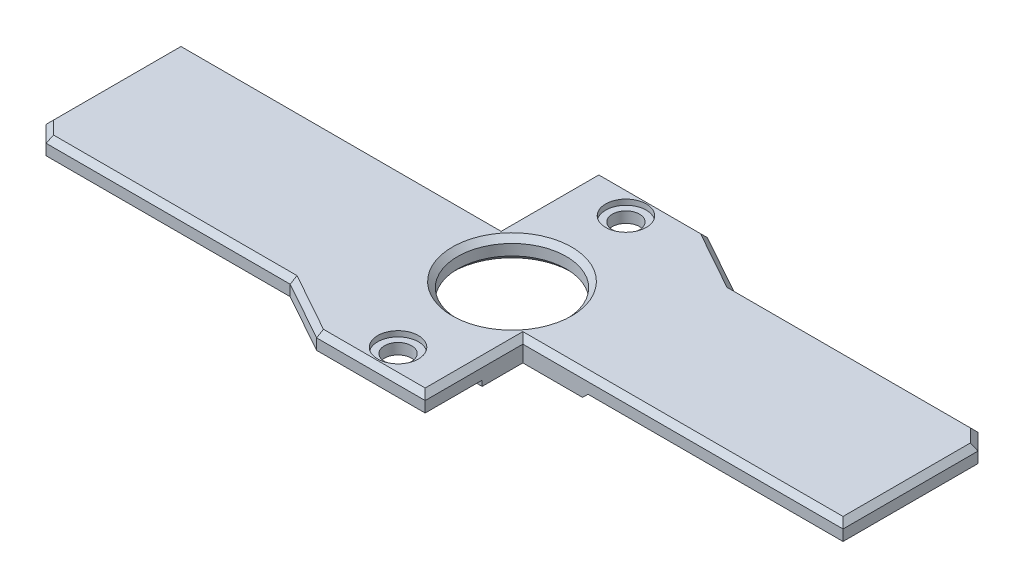
SolidWorks part; units mm, degrees
ref_plane "Front Plane" through (0, 0, 0) normal (0, 0, 1) x (1, 0, 0)
ref_plane "Top Plane" through (0, 0, 0) normal (0, 1, 0) x (1, 0, 0)
ref_plane "Right Plane" through (0, 0, 0) normal (1, 0, 0) x (0, 0, -1)
sketch "Sketch1" plane through (0, 0, 0) normal (0, 1, 0) x (1, 0, 0)
  line L1 (-21, -21) -> (21, -21)
  line L2 (-21, -21) -> (-21, 21)
  line L3 (-21, 21) -> (21, 21)
  line L4 (21, -21) -> (21, 21)
  line L5 (-21, -21) -> (21, 21) construction
  line L6 (-21, 21) -> (21, -21) construction
  point P0 (0, 0)
  dimension "D1" = 42
  dimension "D2" = 42
extrude "Boss-Extrude1" add sketch "Sketch1" along normal blind 2
sketch "Sketch2" plane through (0, 2, 0) normal (0, 1, 0) x (1, 0, 0)
  line L0 (0, 21) -> (0, -21) construction
  line L1 (21, 21) -> (-21, 21) construction
  line L2 (-21, -21) -> (21, -21) construction
  line L3 (-1.1, 0) -> (1.1, 0) construction
  line L4 (-10, -26) -> (10, -26)
  line L5 (-10, -26) -> (-10, -16)
  line L6 (-10, -16) -> (10, -16)
  line L7 (10, -26) -> (10, -16)
  line L8 (-10, -26) -> (10, -16) construction
  line L9 (-10, -16) -> (10, -26) construction
  line L14 (-10, 16) -> (10, 16)
  line L15 (10, 26) -> (10, 16)
  line L16 (-10, 26) -> (10, 26)
  line L17 (-10, 26) -> (-10, 16)
  dimension "D1" = 10
  dimension "D2" = 20
extrude "Boss-Extrude2" add sketch "Sketch2" against normal up to surface (2 mm away) up to face at (0, 0, 0)
sketch "Sketch3" plane through (0, 2, 0) normal (0, 1, 0) x (1, 0, 0)
  circle A0 centre (0, 0) radius 10
  dimension "D1" = 20
extrude "Cut-Extrude1" cut sketch "Sketch3" against normal blind 10
sketch "Sketch4" plane through (0, 2, 0) normal (0, 1, 0) x (1, 0, 0)
  line L0 (-21, 21) -> (-21, -21) construction
  line L1 (21, -21) -> (21, 21) construction
  line L2 (21, -8) -> (-10, -8) construction
  line L5 (0, -1.1) -> (0, 1.1) construction
  line L6 (10, -21) -> (21, -21) construction
  line L7 (21, -21) -> (10, -21)
  line L8 (21, -21) -> (21, -8)
  line L9 (21, -8) -> (10, -8)
  line L10 (10, -21) -> (10, -8)
  line L15 (-1.1, 0) -> (1.1, 0) construction
  line L16 (-21, 21) -> (-21, 8)
  line L17 (-21, 21) -> (-10, 21)
  line L18 (-10, 21) -> (-10, 8)
  line L19 (-21, 8) -> (-10, 8)
  dimension "D1" = 13
  dimension "D2" = 11
extrude "Cut-Extrude2" cut sketch "Sketch4" against normal blind 10
sketch "Sketch5" plane through (0, 2, 0) normal (0, 1, 0) x (1, 0, 0)
  line L0 (-1.1, 0) -> (1.1, 0) construction
  circle A0 centre (0, 21) radius 2.5
  circle A1 centre (0, -21) radius 2.5
  dimension "D1" = 5
extrude "Cut-Extrude3" cut sketch "Sketch5" against normal blind 10
chamfer "Chamfer1" distance 10 angle 45 2 edges at (21, 1, -21) (-21, 1, 21)
sketch "Sketch6" plane through (0, 2, 0) normal (0, 1, 0) x (1, 0, 0)
  line L18 (21, -8) -> (21, 11)
  line L19 (21, 11) -> (11, 21)
  line L20 (11, 21) -> (10, 21)
  line L21 (10, 21) -> (10, 26)
  line L22 (10, 26) -> (-10, 26)
  line L23 (-10, 26) -> (-10, 8)
  line L26 (-10, 8) -> (-21, 8)
  line L27 (-21, 8) -> (-21, -11)
  line L28 (-21, -11) -> (-11, -21)
  line L29 (-11, -21) -> (-10, -21)
  line L30 (-10, -21) -> (-10, -26)
  line L31 (-10, -26) -> (10, -26)
  line L32 (10, -26) -> (10, -8)
  line L35 (10, -8) -> (21, -8)
  line L36 (21, -8) -> (21, 11)
  line L37 (21, 11) -> (11, 21)
  line L38 (11, 21) -> (10, 21)
  line L39 (10, 21) -> (10, 26)
  line L40 (10, 26) -> (-10, 26)
  line L41 (-10, 26) -> (-10, 8)
  line L44 (-10, 8) -> (-21, 8)
  line L45 (-21, 8) -> (-21, -11)
  line L46 (-21, -11) -> (-11, -21)
  line L47 (-11, -21) -> (-10, -21)
  line L48 (-10, -21) -> (-10, -26)
  line L49 (-10, -26) -> (10, -26)
  line L50 (10, -26) -> (10, -8)
  line L53 (10, -8) -> (21, -8)
  circle A0 centre (0, 21) radius 3.75
  circle A1 centre (0, -21) radius 3.75
  circle A2 centre (0, 0) radius 10
  dimension "D2" = 7.5
  dimension "D1" = 0
extrude "Boss-Extrude3" add sketch "Sketch6" along normal blind 1
sketch "Sketch8" plane through (0, 0, 0) normal (0, -1, 0) x (1, 0, 0)
  line L1 (10, -15.5) -> (-10, -15.5)
  line L3 (-10, 15.5) -> (10, 15.5)
  line L4 (10, -26) -> (-10, -26) construction
  line L5 (-10, 26) -> (10, 26) construction
  line L6 (10, -15.5) -> (16.5, -15.5)
  line L7 (-10, 15.5) -> (-16.5, 15.5)
  line L14 (10, -21) -> (11, -21)
  line L15 (11, -21) -> (21, -11)
  line L16 (21, -11) -> (21, 8)
  line L17 (21, 8) -> (10, 8)
  line L18 (10, 8) -> (10, 26)
  line L19 (10, 26) -> (-10, 26)
  line L20 (-10, 26) -> (-10, 21)
  line L21 (-10, 21) -> (-11, 21)
  line L22 (-11, 21) -> (-21, 11)
  line L23 (-21, 11) -> (-21, -8)
  line L24 (-21, -8) -> (-10, -8)
  line L25 (-10, -8) -> (-10, -26)
  line L26 (-10, -26) -> (10, -26)
  line L27 (10, -26) -> (10, -21)
  line L29 (16.5, -15.5) -> (21, -11)
  line L30 (21, -11) -> (21, 8)
  line L31 (21, 8) -> (10, 8)
  line L32 (10, 8) -> (10, 15.5)
  line L36 (-16.5, 15.5) -> (-21, 11)
  line L37 (-21, 11) -> (-21, -8)
  line L38 (-21, -8) -> (-10, -8)
  line L39 (-10, -8) -> (-10, -15.5)
  circle A0 centre (0, 0) radius 10
  dimension "D2" = 10.5
  dimension "D3" = 10.5
  dimension "D1" = 0
extrude "Boss-Extrude4" add sketch "Sketch8" along normal blind 1
sketch "Sketch11" plane through (0, 3, 0) normal (0, 1, 0) x (1, 0, 0)
  line L0 (10, 26) -> (10, -8) construction
  line L1 (21, -8) -> (69, -8)
  line L2 (21, -8) -> (21, 11)
  line L3 (21, 26) -> (69, 26)
  line L4 (69, -8) -> (69, 26)
  line L5 (10, 26) -> (-10, 26) construction
  line L6 (10, 26) -> (21, 26)
  line L7 (10, 26) -> (10, 21)
  line L8 (10, 21) -> (11, 21)
  line L9 (11, 21) -> (21, 11)
  line L10 (0, 26) -> (0, -26) construction
  line L11 (-10, -26) -> (10, -26) construction
  dimension "D1" = 69
extrude "Boss-Extrude5" add sketch "Sketch11" against normal up to surface (3 mm away) up to face at (4.5833, 0, -20.8333)
sketch "Sketch12" plane through (0, 0, 0) normal (0, -1, 0) x (1, 0, 0)
  line L0 (69, -19.87) -> (21, -19.87)
  line L1 (69, 8) -> (69, -26) construction
  line L2 (21, -19.87) -> (10.0031, -26)
  line L3 (69, -26) -> (-10, -26) construction
  line L4 (10.0031, -26) -> (69, -26)
  line L5 (69, -26) -> (69, -19.87)
  dimension "D1" = 48
  dimension "D2" = 12.59
  dimension "D3" = 6.13
extrude "Cut-Extrude6" cut sketch "Sketch12" against normal blind 20
sketch "Sketch14" plane through (0, 3, 0) normal (0, 1, 0) x (1, 0, 0)
  line L0 (-21, 8) -> (-69, 8)
  line L1 (-69, 8) -> (-69, -26)
  line L2 (-69, -26) -> (-10, -26)
  line L3 (-10, -26) -> (-10, -21)
  line L4 (-10, -21) -> (-11, -21)
  line L5 (-11, -21) -> (-21, -11)
  line L6 (-21, -11) -> (-21, 8)
  line L7 (0, 26) -> (0, -26) construction
  dimension "D1" = 69
extrude "Boss-Extrude6" add sketch "Sketch14" against normal up to surface (3 mm away) up to face at (-4.5833, 0, 20.8333)
sketch "Sketch15" plane through (0, 3, 0) normal (0, 1, 0) x (1, 0, 0)
  line L0 (-69, -26) -> (-69, -19.87)
  line L1 (-69, 8) -> (-69, -26) construction
  line L2 (-69, -19.87) -> (-21, -19.87)
  line L3 (-21, -19.87) -> (-10.0031, -26)
  line L4 (-69, -26) -> (10, -26) construction
  line L5 (-10.0031, -26) -> (-69, -26)
  dimension "D1" = 48
  dimension "D2" = 12.59
  dimension "D3" = 6.13
extrude "Cut-Extrude7" cut sketch "Sketch15" against normal blind 20
chamfer "Chamfer2" distance 3 angle 45 2 edges at (69, 1.5, -19.87) (-69, 1.5, 19.87)
chamfer "Chamfer3" distance 1 angle 45 16 edges at (0, -1, -10) (0, 3, 10) (-15.5016, 3, 22.935) (-0.0016, 3, 26) (10, 3, 17) (39.5, 3, 8) (69, 3, -4.435) (67.5, 3, -18.37) (43.5, 3, -19.87) (15.5016, 3, -22.935) (0.0016, 3, -26) (-10, 3, -17) (-39.5, 3, -8) (-43.5, 3, 19.87) (-67.5, 3, 18.37) (-69, 3, 4.435)
chamfer "Chamfer4" distance 1 angle 45 2 edges at (-21, -1, 1.5) (21, 0, -1.5)
ref_plane "Plane2" through (0, 16.5, 0) normal (0, 1, 0) x (1, 0, 0)
sketch "Sketch16" plane through (0, 16.5, 0) normal (0, -1, 0) x (1, 0, 0)
  point P0 (0, 0)
